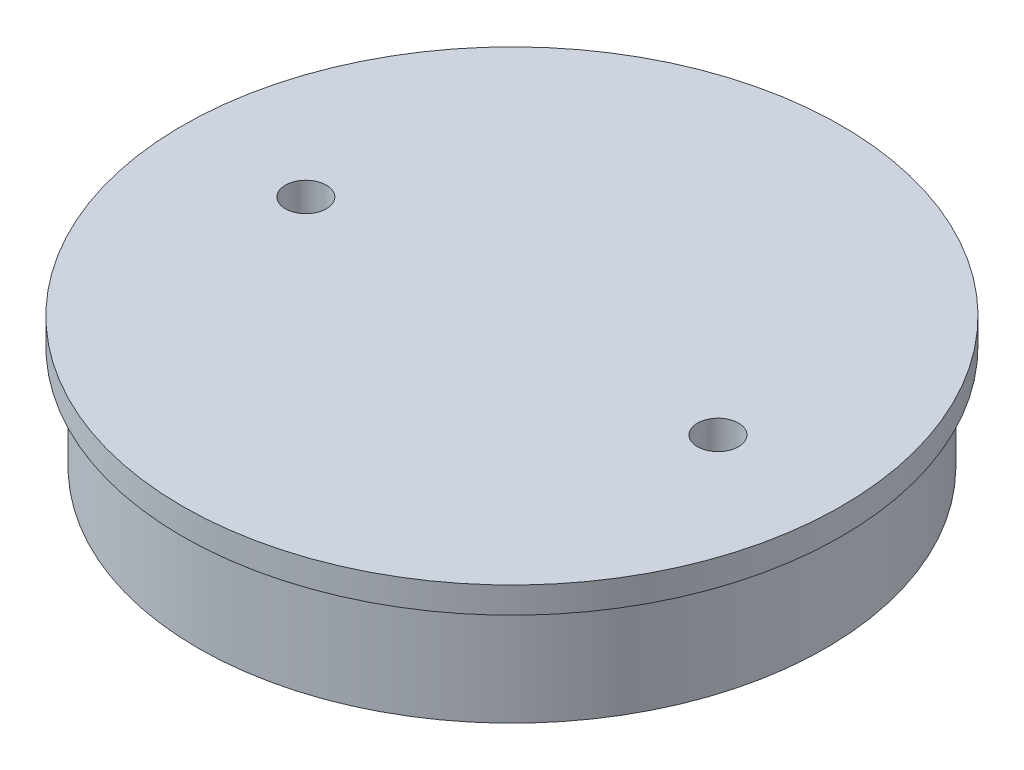
SolidWorks part; units mm, degrees
ref_plane "Front Plane" through (0, 0, 0) normal (0, 0, 1) x (1, 0, 0)
ref_plane "Top Plane" through (0, 0, 0) normal (0, 1, 0) x (1, 0, 0)
ref_plane "Right Plane" through (0, 0, 0) normal (1, 0, 0) x (0, 0, -1)
sketch "Sketch1" plane through (0, 0, 0) normal (0, 1, 0) x (1, 0, 0)
  circle A0 centre (0, 0) radius 38.1
  circle A1 centre (0, 0) radius 40.005
  dimension "D1" = 76.2
  dimension "D2" = 80.01
extrude "Boss-Extrude1" add sketch "Sketch1" along normal blind 3.175 contours A0 | A1 A0 | A0 | A1 region at (0, 0, 0) region at (-38.8735, 0, 0)
extrude "Boss-Extrude2" add sketch "Sketch1<3>" against normal blind 12.7 contours A0 region at (0, 0, 0)
sketch "Sketch1<3>" plane through (0, 0, 0) normal (0, 1, 0) x (1, 0, 0) same geometry as "Sketch1"
sketch "Sketch3" plane through (0, 3.175, 0) normal (0, 1, 0) x (1, 0, 0)
  line L0 (0, 40.005) -> (0, -40.005) construction
  circle A1 centre (-25.015, 0) radius 2.4892
  circle A2 centre (25.015, 0) radius 2.4892
  point P7 (0, 0)
  dimension "D1" = 4.9784
  dimension "D2" = 25.015
extrude "Cut-Extrude1" cut sketch "Sketch3" against normal through all both and the other way through all
